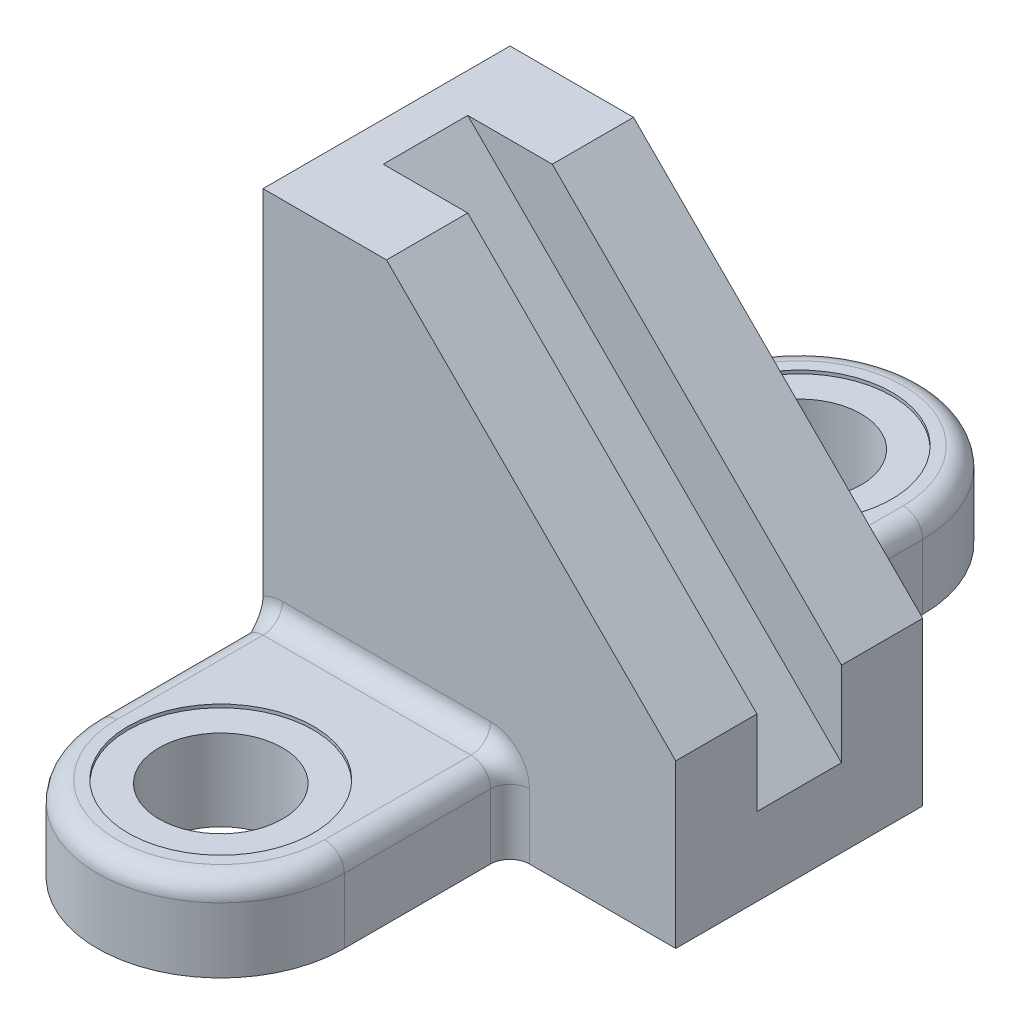
SolidWorks part; units mm, degrees
material "2014 Alloy"
ref_plane "Front Plane" through (0, 0, 0) normal (0, 0, 1) x (1, 0, 0)
ref_plane "Top Plane" through (0, 0, 0) normal (0, 1, 0) x (1, 0, 0)
ref_plane "Right Plane" through (0, 0, 0) normal (1, 0, 0) x (0, 0, -1)
sketch "Croquis2" plane through (0, 0, 0) normal (0, 0, 1) x (1, 0, 0)
  line L0 (0, 0) -> (0, 139)
  line L1 (0, 139) -> (38, 139)
  line L2 (38, 139) -> (127, 50)
  line L3 (127, 50) -> (127, 0)
  line L4 (127, 0) -> (0, 0)
  line L5 (127, 50) -> (38, 50) construction
  dimension "D1" = 50
  dimension "D2" = 127
  dimension "D3" = 38
  dimension "D4" = 45
extrude "Saliente-Extruir1" add sketch "Croquis2" along normal mid plane 76
sketch "Croquis3" plane through (0, 139, 0) normal (0, 1, 0) x (1, 0, 0)
  line L0 (38, 0) -> (38, 13)
  line L1 (38, -38) -> (38, 38) construction
  line L2 (38, 13) -> (12, 13)
  line L3 (12, 13) -> (12, -13)
  line L4 (12, -13) -> (38, -13)
  line L5 (38, -13) -> (38, 0)
  dimension "D1" = 26
  dimension "D2" = 26
  dimension "D3" = 13
sketch "Croquis4" plane through (0, 139, 0) normal (0, 1, 0) x (1, 0, 0)
extrude "Cortar-Extruir1" cut sketch "Croquis3" along direction (-0.7071, 0.7071, 0) on the side against the normal through all
sketch "Croquis10" plane through (0, 0, 0) normal (0, -1, 0) x (1, 0, 0)
  line L0 (0, 38) -> (0, 89)
  line L2 (76, 89) -> (76, 38)
  line L3 (0, 38) -> (127, 38) construction
  line L4 (76, 38) -> (0, 38)
  arc A0 (76, 89) -> (0, 89) centre (38, 89) ccw
  circle A1 centre (38, 89) radius 19
  dimension "D3" = 38
  dimension "D1" = 89
  dimension "D2" = 76
extrude "Saliente-Extruir2" add sketch "Croquis10" against normal blind 26
fillet "Redondeo2" radius 6 3 edges at (0, 26, 63.5) (38, 26, 127) (76, 26, 63.5)
sketch "Croquis12" plane through (0, 26, 0) normal (0, 1, 0) x (1, 0, 0)
  circle A0 centre (38, -89) radius 28.5
  dimension "D1" = 57
extrude "Cortar-Extruir2" cut sketch "Croquis12" against normal blind 1
mirror "Simetría1" about plane through (0, 0, 0) normal (0, 0, 1) of "Redondeo2", "Saliente-Extruir2", "Cortar-Extruir2"
fillet "Redondeo3" radius 6 8 edges at (1.7574, 24.2426, -38) (76, 10, -38) (74.2426, 24.2426, -38) (1.7574, 24.2426, 38) (76, 10, 38) (74.2426, 24.2426, 38) (38, 26, -38) (38, 26, 38)
